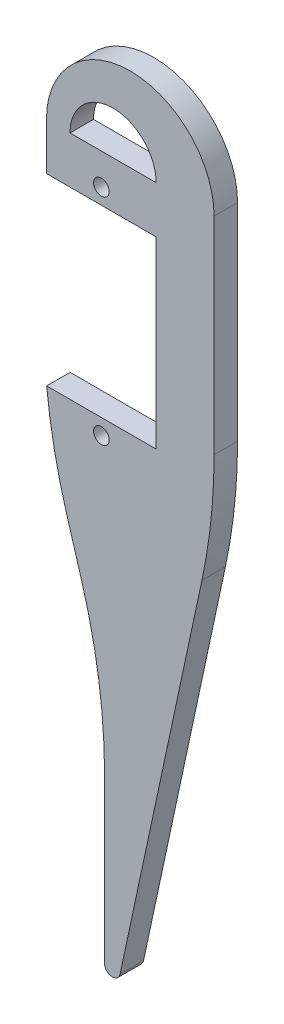
SolidWorks part; units mm, degrees
ref_plane "Front Plane" through (0, 0, 0) normal (0, 0, 1) x (1, 0, 0)
ref_plane "Top Plane" through (0, 0, 0) normal (0, 1, 0) x (1, 0, 0)
ref_plane "Right Plane" through (0, 0, 0) normal (1, 0, 0) x (0, 0, -1)
sketch "Sketch1" plane through (0, 0, 0) normal (0, 0, 1) x (1, 0, 0)
  line L0 (-59.2697, 24.5337) -> (-59.2697, 18.5337)
  line L1 (-59.2697, 18.5337) -> (-45.2478, 18.5337)
  line L2 (-45.2478, 18.5337) -> (-45.2478, -4.9663)
  line L3 (-45.2478, -4.9663) -> (-59.2478, -4.9663)
  line L4 (-59.2478, -4.9663) -> (-59.2478, -9.3071)
  line L5 (-51.8379, -34.0854) -> (-59.2478, -9.3071)
  line L6 (-51.8379, -34.0854) -> (-51.8379, -65.2023)
  line L7 (-49.8601, -65.4118) -> (-37.8382, -9.3071)
  line L8 (-37.8382, -9.3071) -> (-37.8382, 24.5337)
  line L9 (-56.2588, 24.5337) -> (-48.2588, 24.5337) construction
  line L10 (-45.2478, 18.5337) -> (-45.2478, 24.5337) construction
  line L11 (-45.2478, 24.5337) -> (-59.2697, 24.5337) construction
  line L12 (-45.2478, 24.5337) -> (-56.2588, 24.5337)
  arc A0 (-51.8379, -65.2023) -> (-49.8601, -65.4118) centre (-50.8379, -65.2023) ccw
  circle A1 centre (-52.2478, 20.5337) radius 1
  arc A2 (-45.2478, 24.5337) -> (-56.2588, 24.5337) centre (-50.7533, 24.5337) ccw
  arc A3 (-59.2697, 24.5337) -> (-37.8382, 24.5337) centre (-48.554, 24.5337) cw
  circle A8 centre (-52.2478, -6.9663) radius 1
  point P18 (-52.2588, 24.5337)
  dimension "D4" = 2
  dimension "D5" = 2
  dimension "D7" = 2
  dimension "D10" = 27.5
  dimension "D13" = 1
  dimension "D6" = 2
extrude "Boss-Extrude1" add sketch "Sketch1" along normal blind 3
fillet "Скругление2" radius 70 3 edges at (-51.8379, -34.0854, 1.5) (-59.2478, -9.3071, 1.5) (-37.8382, -9.3071, 1.5)
